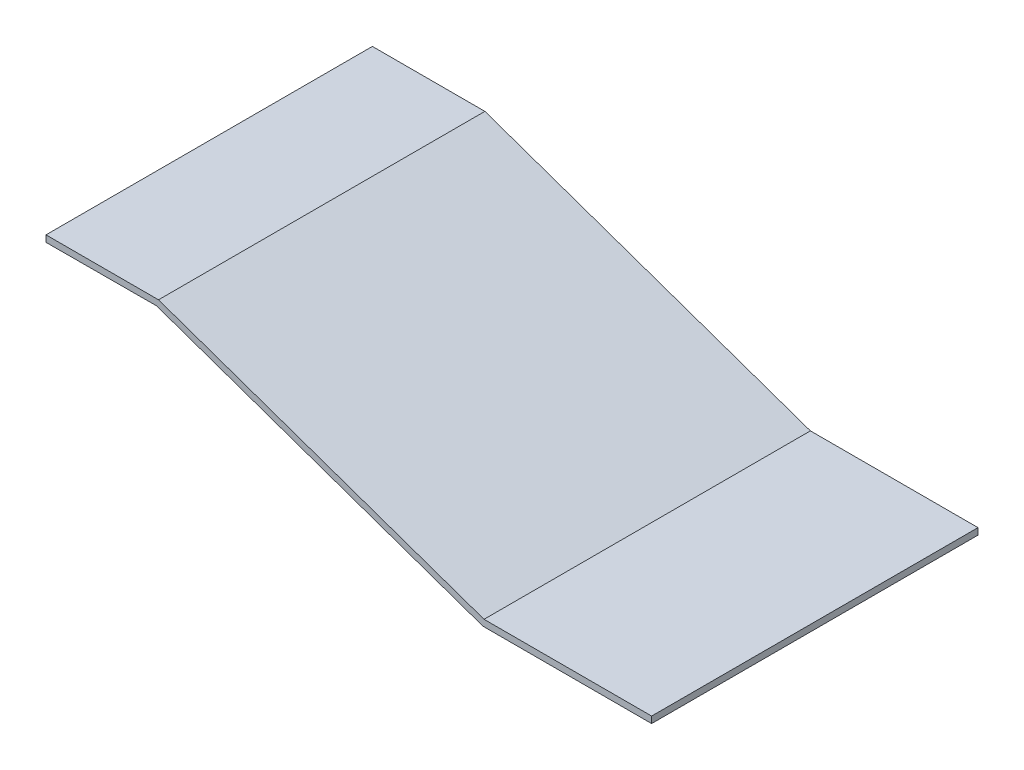
SolidWorks part; units mm, degrees
ref_plane "Front Plane" through (0, 0, 0) normal (0, 0, 1) x (1, 0, 0)
ref_plane "Top Plane" through (0, 0, 0) normal (0, 1, 0) x (1, 0, 0)
ref_plane "Right Plane" through (0, 0, 0) normal (1, 0, 0) x (0, 0, -1)
sketch "Sketch1" plane through (0, 0, 0) normal (0, 0, 1) x (1, 0, 0)
  line L0 (0, 56.6611) -> (0, 76.6611)
  line L1 (0, 76.6611) -> (344.7284, 76.6611)
  line L2 (344.7284, 76.6611) -> (1399.2312, -292.4149)
  line L3 (1399.2312, -292.4149) -> (1338.7195, -292.4149)
  line L4 (1338.7195, -292.4149) -> (338.7195, 57.5851)
  line L5 (338.7195, 57.5851) -> (0, 56.6611)
  line L6 (1338.7195, -292.4149) -> (1338.7195, -272.4149)
  line L7 (1338.7195, -272.4149) -> (1855.5883, -272.4149)
  line L8 (1855.5883, -272.4149) -> (1855.5883, -292.4149)
  line L9 (1855.5883, -292.4149) -> (1338.7195, -292.4149)
  dimension "D1" = 20
  dimension "D2" = 20
  dimension "D4" = 350
  dimension "D5" = 20
  dimension "D6" = 1000
extrude "Boss-Extrude1" add sketch "Sketch1" along normal blind 1000 contours L6 L7 L8 L9 | L4 L5 L0 L1 L2 L3
